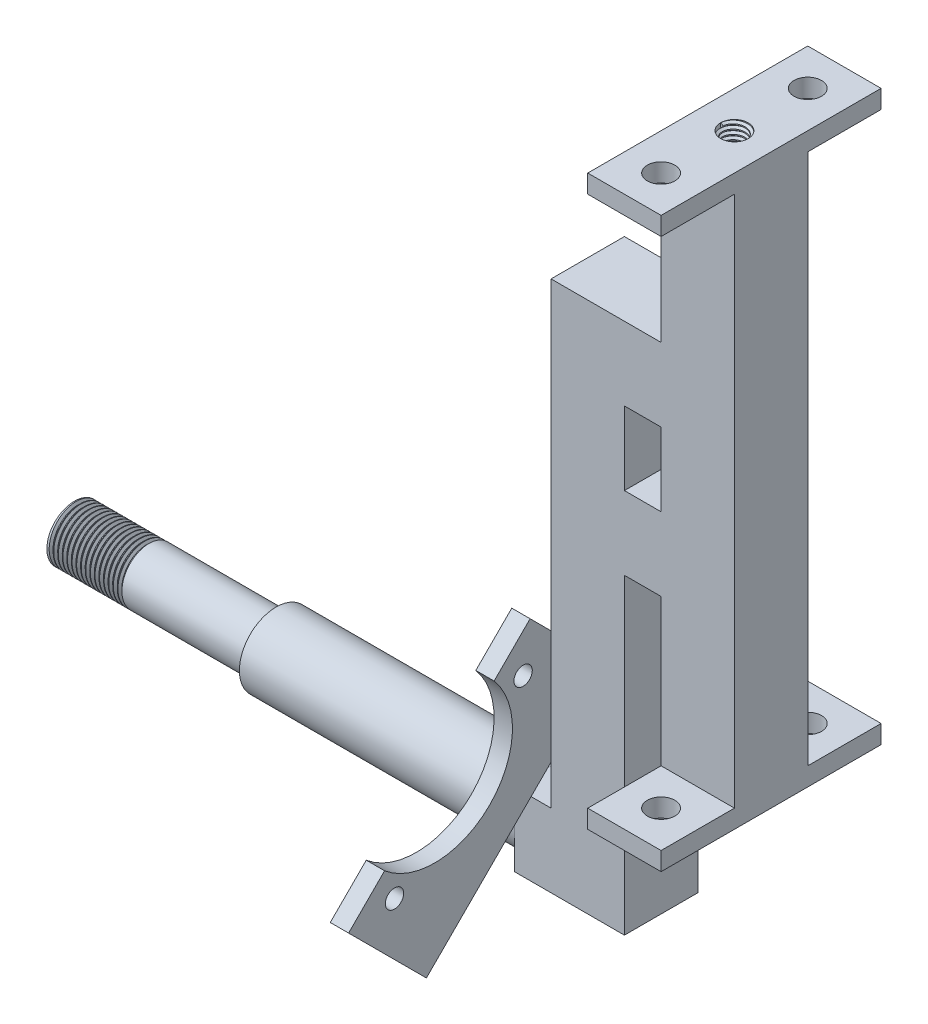
SolidWorks part; units mm, degrees
material "Plain Carbon Steel"
ref_plane "Front Plane" through (0, 0, 0) normal (0, 0, 1) x (1, 0, 0)
ref_plane "Top Plane" through (0, 0, 0) normal (0, 1, 0) x (1, 0, 0)
ref_plane "Right Plane" through (0, 0, 0) normal (1, 0, 0) x (0, 0, -1)
sketch "Sketch1" plane through (0, 0, 0) normal (0, 1, 0) x (1, 0, 0)
  line L1 (12.7, -12.7) -> (-12.7, -12.7)
  line L2 (12.7, -12.7) -> (12.7, 12.7)
  line L3 (12.7, 12.7) -> (-12.7, 12.7)
  line L4 (-12.7, -12.7) -> (-12.7, 12.7)
  line L5 (12.7, -12.7) -> (-12.7, 12.7) construction
  line L6 (12.7, 12.7) -> (-12.7, -12.7) construction
  line L7 (10.16, -10.16) -> (-10.16, -10.16)
  line L8 (10.16, -10.16) -> (10.16, 10.16)
  line L9 (10.16, 10.16) -> (-10.16, 10.16)
  line L10 (-10.16, -10.16) -> (-10.16, 10.16)
  line L11 (10.16, -10.16) -> (-10.16, 10.16) construction
  line L12 (10.16, 10.16) -> (-10.16, -10.16) construction
  point P0 (0, 0)
  point P5 (0, 0)
  dimension "D1" = 2.54
  dimension "1" = 25.4
extrude "Sq_Tb Extrude" add sketch "Sketch1" along normal blind 196.85
sketch "Sketch3" plane through (0, 196.85, 0) normal (0, 1, 0) x (1, 0, 0)
  line L0 (12.7, -12.7) -> (12.7, 12.7) construction
  line L1 (10.16, -10.16) -> (-10.16, -10.16)
  line L2 (10.16, -10.16) -> (10.16, 10.16)
  line L3 (10.16, 10.16) -> (-10.16, 10.16)
  line L4 (-10.16, -10.16) -> (-10.16, 10.16)
  line L5 (10.16, -10.16) -> (-10.16, 10.16) construction
  line L6 (10.16, 10.16) -> (-10.16, -10.16) construction
  line L7 (-12.7, 12.7) -> (12.7, 12.7)
  line L8 (-12.7, 12.7) -> (-12.7, 38.1)
  line L9 (-12.7, 38.1) -> (12.7, 38.1)
  line L10 (12.7, 12.7) -> (12.7, 38.1)
  line L11 (-12.7, 12.7) -> (12.7, 38.1) construction
  line L12 (-12.7, 38.1) -> (12.7, 12.7) construction
  line L13 (0, 0) -> (12.7, 0) construction
  line L14 (-12.7, -38.1) -> (12.7, -12.7) construction
  line L15 (-12.7, -12.7) -> (12.7, -38.1) construction
  line L16 (12.7, -12.7) -> (12.7, -38.1)
  line L17 (-12.7, -38.1) -> (12.7, -38.1)
  line L18 (-12.7, -12.7) -> (-12.7, -38.1)
  line L19 (-12.7, -12.7) -> (12.7, -12.7)
  circle A0 centre (0, 0) radius 4.7625
  circle A1 centre (0, 25.4) radius 4.7625
  circle A2 centre (0, -25.4) radius 4.7625
  point P0 (0, 0)
  point P13 (0, 25.4)
  point P26 (0, -25.4)
  dimension "D1" = 9.525
  dimension "D3" = 50.8
  dimension "D2" = 25.4
extrude "End Caps" add sketch "Sketch3" against normal blind 6.35
ref_plane "Mid-Plane" through (0, 98.425, 0) normal (0, 1, 0) x (1, 0, 0)
mirror "End Cap Mirror" about plane through (0, 98.425, 0) normal (0, 1, 0) of "End Caps"
thread "Top Thread" pitch 1.5875 method extrude profile "Thread Profile1" start angle 0, offset 0, length 0, pitch 1.5875, diameter 9.525
ref_plane "Plane2" through (-4.7625, 196.85, 0) normal (0, 0, 1) x (-1, 0, 0)
sketch "Thread Profile1" plane through (-4.7625, 196.85, 0) normal (0, 0, 1) x (-1, 0, 0)
  line L0 (0, 0) -> (0, 1.5875) construction
  line L11 (0, 0) -> (0, 1.3891)
  line L12 (0, 1.3891) -> (-0.8593, 0.893)
  line L13 (-0.8593, 0.893) -> (-0.8593, 0.4961)
  line L15 (-0.8593, 0.4961) -> (0, 0)
  line L17 (-0.8593, 0.6945) -> (0, 0.6945) construction
  point P2 (0, 0)
  dimension "Pitch" = 1.5875
  dimension "Profile_Angle" = 60
  dimension "Profile_Land" = 0.3969
  dimension "Profile_Height" = 0.8593
thread "Bottom Thread" pitch 1.5875 method extrude profile "Thread Profile2" start angle 0, offset 0, length 0, pitch 1.5875, diameter 9.525
ref_plane "Plane3" through (4.7625, 0, 0) normal (0, 0, 1) x (1, 0, 0)
sketch "Thread Profile2" plane through (4.7625, 0, 0) normal (0, 0, 1) x (1, 0, 0)
  line L0 (0, 0) -> (0, 1.5875) construction
  line L11 (0, 0) -> (0, 1.3891)
  line L12 (0, 1.3891) -> (-0.8593, 0.893)
  line L13 (-0.8593, 0.893) -> (-0.8593, 0.4961)
  line L15 (-0.8593, 0.4961) -> (0, 0)
  line L17 (-0.8593, 0.6945) -> (0, 0.6945) construction
  point P2 (0, 0)
  dimension "Pitch" = 1.5875
  dimension "Profile_Angle" = 60
  dimension "Profile_Land" = 0.3969
  dimension "Profile_Height" = 0.8593
sketch "Sketch9" plane through (0, 0, 0) normal (0, 0, 1) x (1, 0, 0)
  line L1 (-12.7, 190.5) -> (-12.7, 6.35) construction
  line L11 (-25.4, -50.8) -> (-63.5, -50.8)
  line L12 (-63.5, -50.8) -> (-63.5, -25.4)
  line L13 (-63.5, -25.4) -> (-63.1415, -25.4)
  line L15 (-63.5, -38.1) -> (0, -38.1) construction
  line L16 (0, -38.1) -> (0, 0) construction
  line L24 (-25.4, -25.4) -> (-25.4, -50.8)
  line L27 (-25.4, 107.95) -> (-50.8, 107.95) construction
  line L28 (-50.8, 107.95) -> (-50.8, -25.4)
  line L29 (-50.8, 107.95) -> (-50.8, 133.35)
  line L30 (-50.8, 133.35) -> (-12.7, 133.35)
  line L31 (-12.7, 190.5) -> (-12.7, 6.35) construction
  line L32 (-25.4, 107.95) -> (-12.7, 107.95)
  line L33 (-25.4, 57.15) -> (-12.7, 57.15)
  line L34 (-25.4, 82.55) -> (-12.7, 82.55)
  line L35 (-19.05, 82.55) -> (-19.05, 57.15) construction
  line L36 (-25.4, 107.95) -> (-50.8, 133.35) construction
  line L37 (-63.1415, -25.4) -> (-50.8, -25.4)
  line L38 (-50.8, -25.4) -> (-25.4, -25.4) construction
  line L39 (-50.8, -25.4) -> (-25.4, -50.8) construction
  line L40 (-12.7, 133.35) -> (-12.7, 107.95)
  line L41 (12.7, 190.5) -> (-12.7, 190.5) construction
  line L42 (-12.7, 0) -> (12.7, 0) construction
  line L43 (-25.4, 107.95) -> (-25.4, 82.55)
  line L44 (-25.4, 57.15) -> (-25.4, -25.4)
  line L45 (-12.7, 82.55) -> (-12.7, 57.15)
  dimension "D1" = 25.4
  dimension "D2" = 50.8
  dimension "D3" = 25.4
  dimension "D4" = 57.15
  dimension "D5" = 57.15
  dimension "D6" = 50.8
  dimension "D8" = 38.1
extrude "Sq_Tb Angles" add sketch "Sketch9" along normal blind 12.7 and the other way blind 12.7 contours L13 L12 L11 region at (-37.0114, 42.9079, 0)
sketch "Sketch11" plane through (0, 0, 0) normal (0, 0, 1) x (1, 0, 0)
  line L0 (-63.5, -38.1) -> (-228.6, -38.1)
  line L1 (-63.5, -50.8) -> (-63.5, -25.4) construction
  line L2 (-228.6, -38.1) -> (-228.6, -28.575)
  line L3 (-228.6, -28.575) -> (-158.75, -28.575)
  line L4 (-158.75, -28.575) -> (-158.75, -25.4)
  line L5 (-158.75, -25.4) -> (-63.5, -25.4)
  line L6 (-63.5, -25.4) -> (-63.5, -38.1)
  dimension "D1" = 12.7
  dimension "D2" = 9.525
  dimension "D3" = 95.25
  dimension "D4" = 69.85
revolve "Wheel Rod" add sketch "Sketch11" angle 360 about L0
thread "Wheel Threads" pitch 1.5875 method cut profile "Thread Profile3" start angle 0, offset 0, length 25.4, pitch 1.5875, diameter 19.05
ref_plane "Plane4" through (-228.6, -38.1, -9.525) normal (0, -1, 0) x (0, 0, -1)
sketch "Thread Profile3" plane through (-228.6, -38.1, -9.525) normal (0, -1, 0) x (0, 0, -1)
  line L0 (0, 0) -> (0, 1.5875) construction
  line L11 (0, 0) -> (0, 1.3891)
  line L12 (0, 1.3891) -> (-0.8593, 0.893)
  line L13 (-0.8593, 0.893) -> (-0.8593, 0.4961)
  line L15 (-0.8593, 0.4961) -> (0, 0)
  line L17 (-0.8593, 0.6945) -> (0, 0.6945) construction
  point P2 (0, 0)
  dimension "Pitch" = 1.5875
  dimension "Profile_Angle" = 60
  dimension "Profile_Land" = 0.3969
  dimension "Profile_Height" = 0.8593
ref_plane "Tie-Rod Mount Plane" through (0, 44.45, 0) normal (0, 1, 0) x (1, 0, 0)
sketch "Sketch12" plane through (-50.8, 0, 0) normal (-1, 0, 0) x (0, 0, 1)
  line L0 (70.3677, -15.3502) -> (82.8271, -27.8097)
  line L1 (82.8271, -27.8097) -> (55.8864, -54.7505)
  line L2 (55.8864, -54.7505) -> (-6.9754, 8.1113)
  line L3 (24.4555, -23.3196) -> (36.2877, -11.4874) construction
  line L4 (19.9653, 35.0521) -> (-6.9754, 8.1113)
  line L5 (32.4248, 22.5926) -> (19.9653, 35.0521)
  line L6 (32.4248, 22.5926) -> (70.3677, -15.3502)
  line L7 (22.3872, 19.1599) -> (66.9349, -25.3879) construction
  line L8 (24.4555, -23.3196) -> (44.661, -3.114) construction
  line L9 (52.9971, 5.2221) -> (51.3962, 3.6212) construction
  line L11 (12.7, -25.4) -> (12.7, 133.35) construction
  circle A0 centre (66.9349, -25.3879) radius 3.175
  circle A1 centre (22.3872, 19.1599) radius 3.175
  arc A2 (70.3677, -15.3502) -> (32.4248, 22.5926) centre (52.9971, 5.2221) cw
  circle A3 centre (0, -38.1) radius 28.575 construction
  point P11 (66.9349, -25.3879)
  line M12 (12.7, -25.4) -> (12.7, 133.35)
  dimension "D2" = 6.35
  dimension "D3" = 26.925
  dimension "D9" = 57.15
  dimension "D1" = 63
  dimension "D4" = 38.1
  dimension "D5" = 88.9
  dimension "D6" = 16.7333
  dimension "D7" = 28.575
  dimension "D8" = 2.264
  dimension "D10" = 135
extrude "Boss-Extrude1" add sketch "Sketch12" along normal blind 6.35 contours L0 A2 L5 L4 L2 L1 A1 A0 M12 | L4 L2 M12 region at (-50.8, -22.3857, 75.7917) region at (-50.8, 8.1113, 6.1415)
